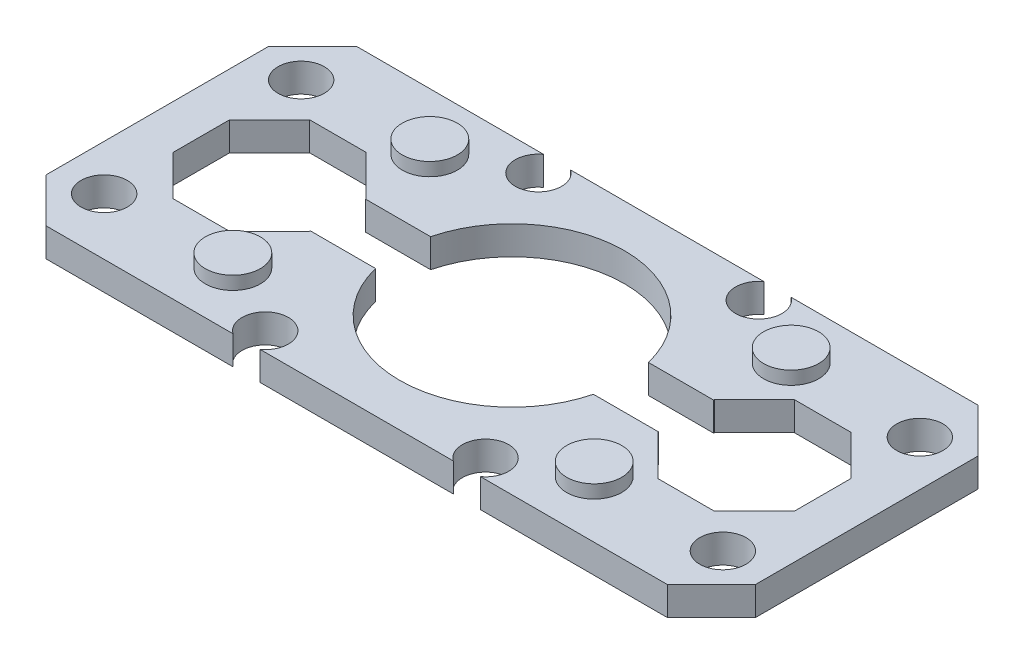
SolidWorks part; units mm, degrees
ref_plane "Front" through (0, 0, 0) normal (0, 0, 1) x (1, 0, 0)
ref_plane "Top" through (0, 0, 0) normal (0, 1, 0) x (1, 0, 0)
ref_plane "Right" through (0, 0, 0) normal (1, 0, 0) x (0, 0, -1)
sketch "Sketch1" plane through (0, 0, 0) normal (0, 1, 0) x (1, 0, 0)
  line L0 (-5.5671, 8.9535) -> (5.5671, 8.9535)
  line L1 (-6.35, -7.874) -> (6.35, -7.874) construction
  line L2 (-6.35, -7.874) -> (-6.35, 7.874) construction
  line L3 (-6.35, 7.874) -> (6.35, 7.874) construction
  line L4 (6.35, -7.874) -> (6.35, 7.874) construction
  line L5 (-6.35, -7.874) -> (6.35, 7.874) construction
  line L6 (-6.35, 7.874) -> (6.35, -7.874) construction
  line L7 (-17.8308, -5.6769) -> (17.8308, -5.6769) construction
  line L8 (-17.8308, -5.6769) -> (-17.8308, 5.6769) construction
  line L9 (-17.8308, 5.6769) -> (17.8308, 5.6769) construction
  line L10 (17.8308, -5.6769) -> (17.8308, 5.6769) construction
  line L11 (-17.8308, -5.6769) -> (17.8308, 5.6769) construction
  line L12 (-17.8308, 5.6769) -> (17.8308, -5.6769) construction
  line L13 (-10.414, -5.6769) -> (10.414, -5.6769) construction
  line L14 (-10.414, -5.6769) -> (-10.414, 5.6769) construction
  line L15 (-10.414, 5.6769) -> (10.414, 5.6769) construction
  line L16 (10.414, -5.6769) -> (10.414, 5.6769) construction
  line L17 (-10.414, -5.6769) -> (10.414, 5.6769) construction
  line L18 (-10.414, 5.6769) -> (10.414, -5.6769) construction
  line L19 (-20.447, -8.9535) -> (-7.1329, -8.9535)
  line L20 (-20.447, -8.9535) -> (-20.447, 8.9535)
  line L21 (-20.447, 8.9535) -> (-7.1329, 8.9535)
  line L22 (20.447, -8.9535) -> (20.447, 8.9535)
  line L23 (-20.447, -8.9535) -> (20.447, 8.9535) construction
  line L24 (-20.447, 8.9535) -> (20.447, -8.9535) construction
  line L25 (7.1329, 8.9535) -> (20.447, 8.9535)
  line L26 (7.1329, -8.9535) -> (20.447, -8.9535)
  line L27 (-5.5671, -8.9535) -> (5.5671, -8.9535)
  circle A0 centre (-17.8308, 5.6769) radius 1.3335
  arc A1 (-7.1329, 8.9535) -> (-5.5671, 8.9535) centre (-6.35, 7.874) ccw
  arc A2 (5.5671, 8.9535) -> (7.1329, 8.9535) centre (6.35, 7.874) ccw
  circle A3 centre (17.8308, 5.6769) radius 1.3335
  circle A4 centre (17.8308, -5.6769) radius 1.3335
  arc A5 (7.1329, -8.9535) -> (5.5671, -8.9535) centre (6.35, -7.874) ccw
  arc A6 (-5.5671, -8.9535) -> (-7.1329, -8.9535) centre (-6.35, -7.874) ccw
  circle A7 centre (-17.8308, -5.6769) radius 1.3335
  circle A8 centre (-10.414, 5.6769) radius 1.5875
  circle A9 centre (10.414, 5.6769) radius 1.5875
  circle A10 centre (10.414, -5.6769) radius 1.5875
  circle A11 centre (-10.414, -5.6769) radius 1.5875
  point P0 (0, 0)
  point P6 (0, 0)
  point P11 (0, 0)
  point P16 (0, 0)
  dimension "D8" = 2.667
  dimension "D9" = 3.175
  dimension "D1" = 12.7
  dimension "D2" = 15.748
  dimension "D3" = 11.3538
  dimension "D4" = 35.6616
  dimension "D5" = 40.894
  dimension "D6" = 17.907
  dimension "D7" = 20.828
extrude "Boss-Extrude1" add sketch "Sketch1" along normal blind 1.651
chamfer "Chamfer1" distance 2.54 angle 45 4 edges at (-20.447, 0.8255, 8.9535) (-20.447, 0.8255, -8.9535) (20.447, 0.8255, -8.9535) (20.447, 0.8255, 8.9535)
extrude "Boss-Extrude2" add sketch "Sketch1<2>" along normal blind 2.413 contours A8 | A9 | A10 | A11
sketch "Sketch1<2>" plane through (0, 0, 0) normal (0, 1, 0) x (1, 0, 0) same geometry as "Sketch1"
extrude "Cut-Extrude1" cut sketch "Sketch1<3>" along normal blind 0.889 contours A11 | A10 | A9 | A8
sketch "Sketch1<3>" plane through (0, 0, 0) normal (0, 1, 0) x (1, 0, 0) same geometry as "Sketch1"
sketch "Sketch2" plane through (0, 1.651, 0) normal (0, 1, 0) x (1, 0, 0)
  line L0 (-10.033, 1.5875) -> (-10.033, 1.6308)
  line L1 (-17.907, -3.937) -> (17.907, -3.937) construction
  line L2 (-17.907, -3.937) -> (-17.907, 3.937) construction
  line L3 (-17.907, 3.937) -> (17.907, 3.937) construction
  line L4 (17.907, -3.937) -> (17.907, 3.937) construction
  line L5 (-17.907, -3.937) -> (17.907, 3.937) construction
  line L6 (-17.907, 3.937) -> (17.907, -3.937) construction
  line L7 (-17.907, 1.6308) -> (-17.907, -1.6308)
  line L8 (-17.907, -1.6308) -> (-15.6008, -3.937)
  line L9 (-15.6008, -3.937) -> (-12.3392, -3.937)
  line L10 (-12.3392, -3.937) -> (-10.033, -1.6308)
  line L11 (-10.033, -1.6308) -> (-10.033, -1.5875)
  line L12 (-10.033, 1.6308) -> (-12.3392, 3.937)
  line L13 (-12.3392, 3.937) -> (-15.6008, 3.937)
  line L14 (-15.6008, 3.937) -> (-17.907, 1.6308)
  line L15 (17.907, 1.6308) -> (15.6008, 3.937)
  line L16 (15.6008, 3.937) -> (12.3392, 3.937)
  line L17 (12.3392, 3.937) -> (10.033, 1.6308)
  line L18 (10.033, 1.6308) -> (10.033, 1.5875)
  line L19 (10.033, -1.6308) -> (12.3392, -3.937)
  line L20 (12.3392, -3.937) -> (15.6008, -3.937)
  line L21 (15.6008, -3.937) -> (17.907, -1.6308)
  line L22 (17.907, -1.6308) -> (17.907, 1.6308)
  line L23 (-10.033, -1.5875) -> (-6.2794, -1.5875)
  line L25 (-10.033, 1.5875) -> (-6.2794, 1.5875)
  line L27 (-10.033, -1.5875) -> (10.033, 1.5875) construction
  line L28 (-10.033, 1.5875) -> (10.033, -1.5875) construction
  line L29 (10.033, -1.5875) -> (10.033, -1.6308)
  line L30 (6.2794, 1.5875) -> (10.033, 1.5875)
  line L31 (6.2794, -1.5875) -> (10.033, -1.5875)
  arc A0 (-6.2794, -1.5875) -> (6.2794, -1.5875) centre (0, 0) ccw
  circle A1 centre (-13.97, 0) radius 3.937 construction
  circle A2 centre (13.97, 0) radius 3.937 construction
  arc A4 (6.2794, 1.5875) -> (-6.2794, 1.5875) centre (0, 0) ccw
  dimension "D1" = 12.954
  dimension "D2" = 35.814
  dimension "D3" = 7.874
  dimension "D4" = 3.175
extrude "Cut-Extrude2" cut sketch "Sketch2" against normal through all
